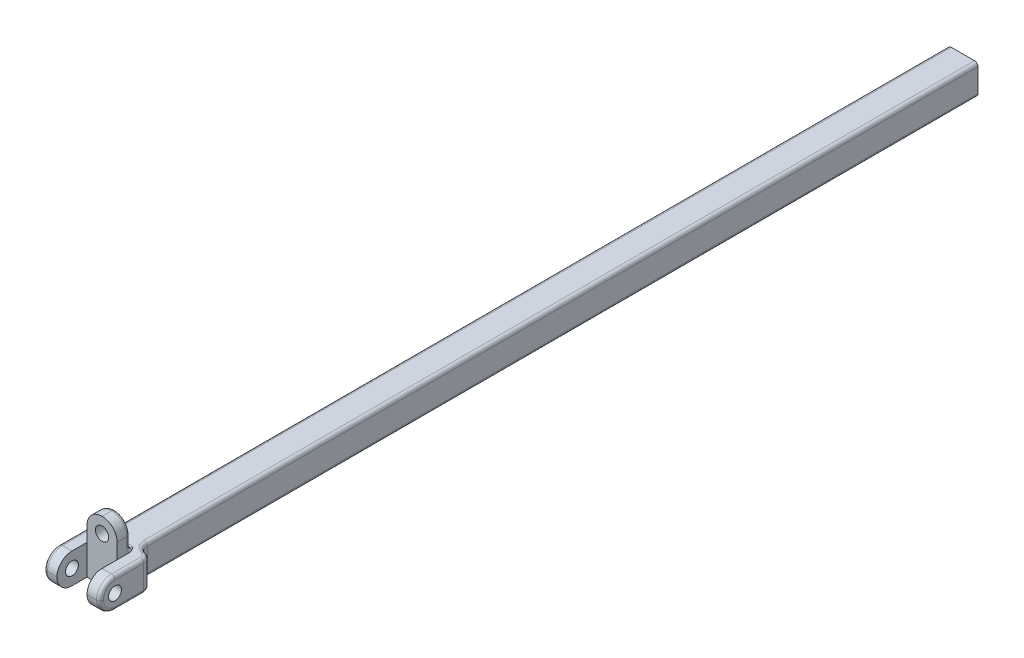
SolidWorks part; units mm, degrees
ref_plane "前视基准面" through (0, 0, 0) normal (0, 0, 1) x (1, 0, 0)
ref_plane "上视基准面" through (0, 0, 0) normal (0, 1, 0) x (1, 0, 0)
ref_plane "右视基准面" through (0, 0, 0) normal (1, 0, 0) x (0, 0, -1)
sketch "草图1" plane through (0, 0, 0) normal (0, 0, 1) x (1, 0, 0)
  line L1 (-3.5, 3.5) -> (3.5, 3.5)
  line L2 (-3.5, 3.5) -> (-3.5, -3.5)
  line L3 (-3.5, -3.5) -> (3.5, -3.5)
  line L4 (3.5, 3.5) -> (3.5, -3.5)
  line L5 (-3.5, 3.5) -> (3.5, -3.5) construction
  line L6 (-3.5, -3.5) -> (3.5, 3.5) construction
  point P0 (0, 0)
  dimension "D1" = 7
  dimension "D2" = 7
extrude "凸台-拉伸1" add sketch "草图1" along normal blind 200
sketch "草图2" plane through (0, 0, 200) normal (0, 0, 1) x (1, 0, 0)
  line L0 (-3.5, 3.5) -> (6.5, 3.5)
  line L1 (6.5, 3.5) -> (6.5, -3.5)
  line L2 (6.5, -3.5) -> (-6.5, -3.5)
  line L3 (-6.5, -3.5) -> (-6.5, 3.5)
  line L4 (-6.5, 3.5) -> (-3.5, 3.5)
  dimension "D1" = 10
  dimension "D2" = 7
  dimension "D3" = 13
extrude "凸台-拉伸2" add sketch "草图2" along normal blind 7 and the other way blind 5
sketch "草图3" plane through (0, 0, 207) normal (0, 0, 1) x (1, 0, 0)
  line L0 (0, 3.5) -> (-3.5, 3.5)
  line L1 (6.5, 3.5) -> (-6.5, 3.5) construction
  line L2 (0, 3.5) -> (3.5, 3.5)
  line L3 (-3.5, 3.5) -> (-3.5, -3.5)
  line L4 (-6.5, -3.5) -> (6.5, -3.5) construction
  line L5 (-3.5, -3.5) -> (3.5, -3.5)
  line L6 (3.5, -3.5) -> (3.5, 3.5)
  dimension "D1" = 3.5
  dimension "D2" = 3.5
extrude "切除-拉伸1" cut sketch "草图3" against normal blind 7
fillet "圆角1" radius 3.5 4 edges at (-5, -3.5, 207) (5, -3.5, 207) (5, 3.5, 207) (-5, 3.5, 207)
sketch "草图4" plane through (0, 3.5, 0) normal (0, 1, 0) x (1, 0, 0)
  line L0 (-3.5, -200) -> (-3.5, -197)
  line L1 (-3.5, -197) -> (3.5, -197)
  line L2 (3.5, -197) -> (3.5, -200)
  line L3 (3.5, -200) -> (-3.5, -200)
  dimension "D1" = 3
  dimension "D2" = 7
extrude "凸台-拉伸3" add sketch "草图4" along normal blind 7
fillet "圆角2" radius 3.5 2 edges at (3.5, 10.5, 198.5) (-3.5, 10.5, 198.5)
sketch "草图5" plane through (0, 0, 197) normal (0, 0, -1) x (-1, 0, 0)
  circle A0 centre (0, 7) radius 1.55
  dimension "D1" = 3.1
extrude "切除-拉伸2" cut sketch "草图5" against normal through all
fillet "圆角3" radius 1.5 1 edges at (0, 3.5, 197)
fillet "圆角4" radius 2 2 edges at (3.5, 0, 195) (-3.5, 0, 195)
fillet "圆角5" radius 2 2 edges at (6.5, 0, 195) (-6.5, 0, 195)
sketch "草图6" plane through (-6.5, 0, 0) normal (-1, 0, 0) x (0, 0, 1)
  circle A0 centre (203.5, 0) radius 1.5
  dimension "D1" = 3
extrude "切除-拉伸3" cut sketch "草图6" against normal through all
fillet "圆角6" radius 0.8 26 edges at (3.5, 3.9393, 196.5607) (3.5, 6, 197) (2.4749, 9.4749, 197) (-2.4749, 9.4749, 197) (-3.5, 3.9393, 196.5607) (3.5, -3.5, 96.5) (3.9189, -3.5, 194.2247) (6.0811, -3.5, 195.6482) (6.5, -3.5, 200.1865) (6.5, -2.4749, 205.9749) (6.5, 2.4749, 205.9749) (6.5, 3.5, 200.1865) (6.0811, 3.5, 195.6482) (3.9189, 3.5, 194.2247) (-3.5, -3.5, 96.5) (-3.9189, -3.5, 194.2247) (-6.0811, -3.5, 195.6482) (-6.5, -3.5, 200.1865) (-6.5, -2.4749, 205.9749) (-6.5, 2.4749, 205.9749) (-6.5, 3.5, 200.1865) (-6.0811, 3.5, 195.6482) (-3.9189, 3.5, 194.2247) (-3.5, 6, 197) (3.5, 3.5, 96.5) (-3.5, 3.5, 96.5)
